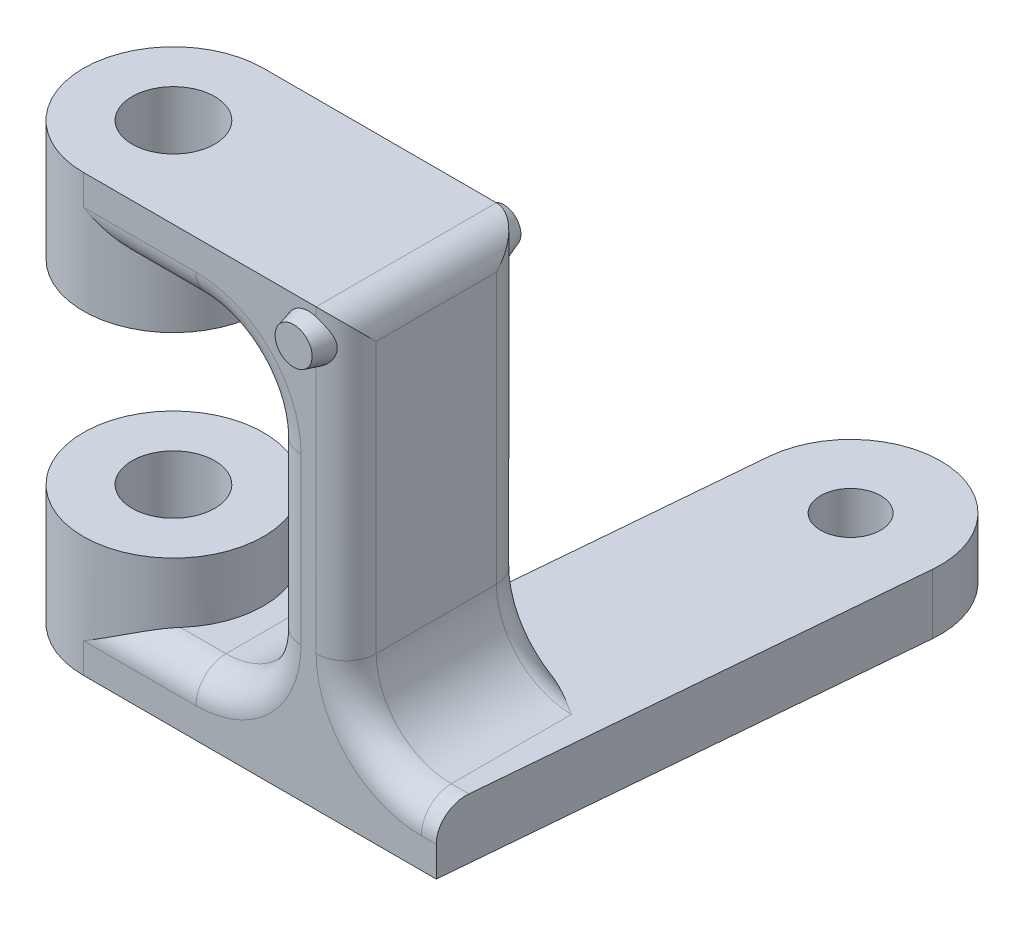
SolidWorks part; units mm, degrees
ref_plane "Front Plane" through (0, 0, 0) normal (0, 0, 1) x (1, 0, 0)
ref_plane "Top Plane" through (0, 0, 0) normal (0, 1, 0) x (1, 0, 0)
ref_plane "Right Plane" through (0, 0, 0) normal (1, 0, 0) x (0, 0, -1)
sketch "Sketch1" plane through (0, 0, 0) normal (0, 1, 0) x (1, 0, 0)
  line L0 (0, 0) -> (18, 0) construction
  line L1 (18, 0) -> (20.1789, 24.9049) construction
  line L2 (0, -6) -> (23.498, -6)
  line L3 (23.498, -6) -> (26.1561, 24.3819)
  line L4 (0, 6) -> (12.502, 6)
  line L5 (12.502, 6) -> (14.2017, 25.4278)
  circle A0 centre (0, 0) radius 6
  circle A1 centre (20.1789, 24.9049) radius 2
  circle A2 centre (20.1789, 24.9049) radius 6
  dimension "D1" = 4
  dimension "D2" = 4
  dimension "D3" = 12
  dimension "D4" = 18
  dimension "D5" = 25
  dimension "D6" = 95
  dimension "D7" = 6
  dimension "D8" = 6
extrude "Boss-Extrude1" add sketch "Sketch1" along normal blind 4
sketch "Sketch3" plane through (0, 4, 0) normal (0, 1, 0) x (1, 0, 0)
  circle A0 centre (0, 0) radius 2.75
  circle A1 centre (0, 0) radius 6
  dimension "D1" = 5.5
extrude "Boss-Extrude2" add sketch "Sketch3" along normal blind 4
sketch "Sketch4" plane through (0, 4, 0) normal (0, 1, 0) x (1, 0, 0)
  line L0 (0, 0) -> (15, 0) construction
  line L1 (0, 6) -> (12.502, 6) construction
  line L2 (17.5, -6) -> (12.5, -6)
  line L3 (17.5, -6) -> (17.5, 6)
  line L4 (17.5, 6) -> (12.5, 6)
  line L5 (12.5, -6) -> (12.5, 6)
  line L6 (17.5, -6) -> (12.5, 6) construction
  line L7 (17.5, 6) -> (12.5, -6) construction
  dimension "D1" = 15
  dimension "D2" = 5
extrude "Boss-Extrude3" add sketch "Sketch4" along normal blind 25
sketch "Sketch5" plane through (0, 29, 0) normal (0, 1, 0) x (1, 0, 0)
  line L0 (0, 6) -> (17.5, 6)
  line L1 (17.5, 6) -> (17.5, -6)
  line L2 (17.5, -6) -> (0, -6)
  circle A0 centre (0, 0) radius 2.75
  circle A1 centre (0, 0) radius 6
  line M2 (12.5, 6) -> (12.5, -6)
  line M3 (12.5, -6) -> (17.5, -6)
  line M4 (17.5, -6) -> (17.5, 6)
  line M5 (17.5, 6) -> (12.5, 6)
extrude "Boss-Extrude4" add sketch "Sketch5" against normal blind 4 contours A1 L2 L0 M2 | A1 A0 | M5 M2 M3 M4
sketch "Sketch6" plane through (0, 25, 0) normal (0, -1, 0) x (1, 0, 0)
  circle A0 centre (0, 0) radius 2.75
  circle A1 centre (0, 0) radius 6
extrude "Boss-Extrude5" add sketch "Sketch6" along normal blind 4
sketch "Sketch7" plane through (0, 0, 6) normal (0, 0, 1) x (1, 0, 0)
  line L0 (12.5, 25) -> (17.5, 29) construction
  circle A0 centre (15, 27) radius 1.5
  dimension "D1" = 3
extrude "Boss-Extrude6" add sketch "Sketch7" along normal blind 1 draft 15
sketch "Sketch8" plane through (0, 0, -6) normal (0, 0, -1) x (-1, 0, 0)
  line L0 (-17.5, 29) -> (-12.5, 25) construction
  circle A0 centre (-15, 27) radius 1.5
  dimension "D1" = 3
extrude "Boss-Extrude7" add sketch "Sketch8" along normal blind 1 draft 20
sketch "Sketch9" plane through (0, 0, 6) normal (0, 0, 1) x (1, 0, 0)
  line L0 (15, 27) -> (-6, 27) construction
  line L1 (-6, 29) -> (-6, 21) construction
  line L3 (-5, 26.25) -> (-6, 26.25)
  line L4 (-5, 26.25) -> (-5, 27.75)
  line L5 (-5, 27.75) -> (-6, 27.75)
  line L6 (-6, 26.25) -> (-6, 27.75)
  line L7 (-5, 26.25) -> (-6, 27.75) construction
  line L8 (-5, 27.75) -> (-6, 26.25) construction
  point P5 (-5.5, 27)
  dimension "D1" = 0.5
  dimension "D2" = 1
  dimension "D3" = 1.5
extrude "Cut-Extrude1" cut sketch "Sketch9" against normal through all
fillet "Fillet1" radius 5 3 edges at (17.5, 4, 0) (12.5, 25, 0) (12.5, 4, 0)
fillet "Fillet2" radius 2 16 edges at (3.75, 25, -6) (3.75, 25, 6) (11.0355, 23.5355, -6) (3.75, 4, -6) (11.0355, 5.4645, -6) (18.9645, 5.4645, -6) (22.999, 4, 6) (17.5, 19, 6) (11.0355, 23.5355, 6) (3.75, 4, 6) (11.0355, 5.4645, 6) (12.5, 14.5, -6) (17.5, 19, -6) (18.9645, 5.4645, 6) (12.5, 14.5, 6) (17.5, 29, 0)
